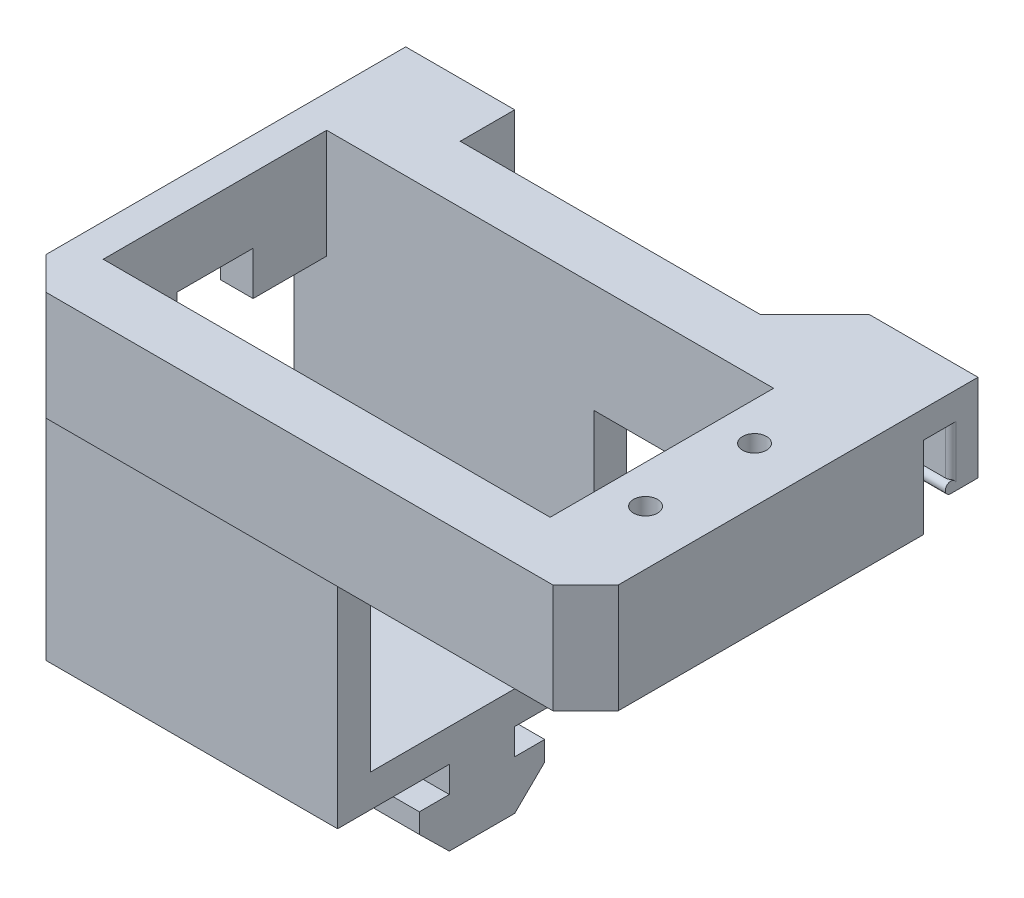
SolidWorks part; units mm, degrees
ref_plane "Alzado" through (0, 0, 0) normal (0, 0, 1) x (1, 0, 0)
ref_plane "Planta" through (0, 0, 0) normal (0, 1, 0) x (1, 0, 0)
ref_plane "Vista lateral" through (0, 0, 0) normal (1, 0, 0) x (0, 0, -1)
sketch "Croquis1" plane through (0, 0, 0) normal (0, 1, 0) x (1, 0, 0)
  line L1 (-24, 5) -> (24, 5) construction
  line L2 (-24, 5) -> (-24, -5) construction
  line L3 (-24, -5) -> (24, -5) construction
  line L4 (24, 5) -> (24, -5) construction
  line L5 (-24, 5) -> (24, -5) construction
  line L6 (-24, -5) -> (24, 5) construction
  line L7 (-20.5, 10.25) -> (20.5, 10.25)
  line L8 (-20.5, 10.25) -> (-20.5, -10.25)
  line L9 (-20.5, -10.25) -> (20.5, -10.25)
  line L10 (20.5, 10.25) -> (20.5, -10.25)
  line L11 (-20.5, 10.25) -> (20.5, -10.25) construction
  line L12 (-20.5, -10.25) -> (20.5, 10.25) construction
  line L13 (-29, 15.5) -> (29, 15.5)
  line L14 (-29, 15.5) -> (-29, -15.5)
  line L15 (-29, -15.5) -> (29, -15.5)
  line L16 (29, 15.5) -> (29, -15.5)
  line L17 (-29, 15.5) -> (29, -15.5) construction
  line L18 (-29, -15.5) -> (29, 15.5) construction
  circle A0 centre (-24, -5) radius 1.1
  circle A1 centre (24, -5) radius 1.1
  circle A2 centre (24, 5) radius 1.1
  circle A3 centre (-24, 5) radius 1.1
  point P0 (0, 0)
  point P10 (0, 0)
  point P15 (0, 0)
  dimension "D3" = 2.2
  dimension "D1" = 48
  dimension "D2" = 10
  dimension "D4" = 41
  dimension "D5" = 20.5
  dimension "D6" = 31
  dimension "D7" = 58
extrude "Saliente-Extruir1" add sketch "Croquis1" along normal blind 10
sketch "Croquis2" plane through (-29, 0, 0) normal (-1, 0, 0) x (0, 0, 1)
  line L0 (0, 0) -> (0, -9.25) construction
  line L1 (-15.5, 0) -> (15.5, 0) construction
  line L2 (-10.25, 10) -> (10.25, 10) construction
  line L3 (-10.25, -18.5) -> (10.25, -18.5)
  line L4 (-10.25, -18.5) -> (-10.25, 0)
  line L5 (-10.25, 0) -> (10.25, 0)
  line L6 (10.25, -18.5) -> (10.25, 0)
  line L7 (-10.25, -18.5) -> (10.25, 0) construction
  line L8 (-10.25, 0) -> (10.25, -18.5) construction
  line L9 (-10.25, 10) -> (10.25, 10) construction
  line L10 (-13.25, 0) -> (-13.25, -21.5)
  line L11 (-13.25, -21.5) -> (-3, -21.5)
  line L12 (13.25, -21.5) -> (13.25, 0)
  line L13 (13.25, 0) -> (10.25, 0)
  line L14 (-13.25, 0) -> (-10.25, 0)
  line L15 (-10.25, -18.5) -> (-10.25, -21.5) construction
  line L16 (0, -9.25) -> (0, -23.9) construction
  line L17 (-5.75, -23.9) -> (5.75, -23.9) construction
  line L18 (-3, -21.5) -> (-3, -23.9)
  line L19 (-3, -23.9) -> (-5.75, -23.9)
  line L20 (3, -21.5) -> (3, -23.9)
  line L21 (3, -23.9) -> (5.75, -23.9)
  line L22 (3, -21.5) -> (13.25, -21.5)
  line L23 (3, -21.5) -> (0, -21.5) construction
  line L24 (0, -21.5) -> (-3, -21.5) construction
  line L25 (-5.75, -23.9) -> (-5.75, -25.7)
  line L26 (-5.75, -25.7) -> (-3, -28.4)
  line L27 (-3, -28.4) -> (3, -28.4)
  line L28 (3, -28.4) -> (5.75, -25.7)
  line L29 (5.75, -25.7) -> (5.75, -23.9)
  point P20 (0, -23.9)
  line M21 (-15.5, 0) -> (15.5, 0)
  dimension "D1" = 18.5
  dimension "D2" = 3
  dimension "D3" = 3
  dimension "D4" = 6
  dimension "D5" = 1.8
  dimension "D6" = 4.5
  dimension "D7" = 11.5
  dimension "D8" = 2.4
  dimension "D9" = 6
extrude "Saliente-Extruir2" add sketch "Croquis2" against normal blind 33 contours L28 L29 L21 L20 L22 L12 L6 L3 L4 L10 L11 L18 L19 L25 L26 L27 M21 region at (-29, -18.8884, 0)
sketch "Croquis3" plane through (0, 0, 13.25) normal (0, 0, 1) x (1, 0, 0)
  circle A0 centre (-9.7378, -26.4) radius 2.1
  dimension "D1" = 4.2
extrude "Cortar-Extruir1" cut sketch "Croquis3" against normal through all
sketch "Croquis4" plane through (-29, 0, 0) normal (-1, 0, 0) x (0, 0, 1)
  line L0 (-10.25, -18.5) -> (10.25, -18.5) construction
  line L1 (10.25, -18.5) -> (10.25, 0) construction
  line L2 (-10.25, 0) -> (10.25, 0) construction
  line L3 (-10.25, -18.5) -> (-10.25, 0) construction
  line L4 (-10.25, -18.5) -> (10.25, -18.5)
  line L5 (10.25, -18.5) -> (10.25, 0)
  line L6 (-10.25, 0) -> (10.25, 0)
  line L7 (-10.25, -18.5) -> (-10.25, 0)
  line L18 (-15.5, 0) -> (-13.25, 0)
  line L19 (-13.25, 0) -> (-13.25, -21.5)
  line L20 (-13.25, -21.5) -> (-3, -21.5)
  line L21 (-3, -21.5) -> (-3, -23.9)
  line L22 (-3, -23.9) -> (-5.75, -23.9)
  line L23 (-5.75, -23.9) -> (-5.75, -25.7)
  line L24 (-5.75, -25.7) -> (-3, -28.4)
  line L25 (-3, -28.4) -> (3, -28.4)
  line L26 (3, -28.4) -> (5.75, -25.7)
  line L27 (5.75, -25.7) -> (5.75, -23.9)
  line L28 (5.75, -23.9) -> (3, -23.9)
  line L29 (3, -23.9) -> (3, -21.5)
  line L30 (3, -21.5) -> (13.25, -21.5)
  line L31 (13.25, -21.5) -> (13.25, 0)
  line L33 (15.5, 0) -> (15.5, 10)
  line L34 (-15.5, 0) -> (-13.25, 0)
  line L35 (-15.5, 10) -> (-15.5, 0)
  line L37 (-13.25, 0) -> (-13.25, -21.5)
  line L38 (-13.25, -21.5) -> (-3, -21.5)
  line L39 (-3, -21.5) -> (-3, -23.9)
  line L40 (-3, -23.9) -> (-5.75, -23.9)
  line L41 (-5.75, -23.9) -> (-5.75, -25.7)
  line L42 (-5.75, -25.7) -> (-3, -28.4)
  line L43 (-3, -28.4) -> (3, -28.4)
  line L44 (3, -28.4) -> (5.75, -25.7)
  line L45 (5.75, -25.7) -> (5.75, -23.9)
  line L46 (5.75, -23.9) -> (3, -23.9)
  line L47 (3, -23.9) -> (3, -21.5)
  line L48 (3, -21.5) -> (13.25, -21.5)
  line L49 (13.25, -21.5) -> (13.25, 0)
  line L51 (15.5, 0) -> (15.5, 10)
  line L53 (-15.5, 10) -> (-15.5, 0)
  line L63 (13.25, 0) -> (15.5, 0)
  line L65 (13.25, 0) -> (15.5, 0)
  line L66 (15.5, 10) -> (-15.5, 10)
  line L67 (15.5, 10) -> (-15.5, 10)
  dimension "D1" = 0
extrude "Cortar-Extruir2" cut sketch "Croquis4" against normal blind 5.5
chamfer "Chaflán1" distance 1.5 angle 45 1 edges at (-23.5, -18.5, 0)
chamfer "Chaflán2" distance 2 angle 45 2 edges at (-9.75, 0, 13.25) (-9.75, 0, -13.25)
sketch "Croquis5" plane through (0, 0, 0) normal (0, -1, 0) x (1, 0, 0)
  line L1 (-20.5, 10.25) -> (-23.5, 10.25)
  line L2 (-20.5, 10.25) -> (-20.5, -10.25)
  line L3 (-20.5, -10.25) -> (-23.5, -10.25)
  line L4 (-23.5, 10.25) -> (-23.5, -10.25)
extrude "Saliente-Extruir3" add sketch "Croquis5" against normal up to surface (10 mm away) up to face at (24, 10, -3.9)
sketch "Croquis6" plane through (-23.5, 0, 0) normal (-1, 0, 0) x (0, 0, 1)
  line L0 (0, 0) -> (0, 10) construction
  line L1 (10.25, 0) -> (-10.25, 0) construction
  line L2 (15.5, 10) -> (-15.5, 10) construction
  line L4 (3.5, 4) -> (-3.5, 4)
  line L5 (3.5, 4) -> (3.5, 0)
  line L6 (3.5, 0) -> (-3.5, 0)
  line L7 (-3.5, 4) -> (-3.5, 0)
  line L8 (3.5, 4) -> (-3.5, 0) construction
  line L9 (3.5, 0) -> (-3.5, 4) construction
  point P6 (0, 2)
  dimension "D1" = 6
  dimension "D2" = 7
extrude "Cortar-Extruir3" cut sketch "Croquis6" against normal up to next
sketch "Croquis7" plane through (0, -28.4, 0) normal (0, -1, 0) x (1, 0, 0)
  line L0 (-10.3781, 0) -> (-9.0975, 0) construction
  line L1 (-10.3781, 3) -> (-10.3781, -3) construction
  line L2 (-9.0975, -3) -> (-9.0975, 3) construction
  line L3 (-10.3781, 3) -> (-23.5, 3) construction
  line L4 (-7.7378, -3) -> (-11.7378, -3)
  line L5 (-7.7378, -3) -> (-7.7378, 3)
  line L6 (-7.7378, 3) -> (-11.7378, 3)
  line L7 (-11.7378, -3) -> (-11.7378, 3)
  line L8 (-7.7378, -3) -> (-11.7378, 3) construction
  line L9 (-7.7378, 3) -> (-11.7378, -3) construction
  point P6 (-9.7378, 0)
  dimension "D1" = 4
extrude "Saliente-Extruir4" add sketch "Croquis7" against normal blind 0.5
chamfer "Chaflán3" distance 3 angle 45 2 edges at (-23.5, 5, 15.5) (29, 5, 15.5)
ref_plane "Plano1" through (29, 0, 0) normal (1, 0, 0) x (0, 0, -1)
sketch "Croquis8" plane through (29, 0, 0) normal (1, 0, 0) x (0, 0, -1)
  line L1 (15.5, 7.5) -> (18, 7.5)
  line L2 (15.5, 7.5) -> (15.5, 3)
  line L3 (15.5, 3) -> (18, 3)
  line L4 (18, 7.5) -> (18, 3)
  line L5 (18, 2) -> (20.5, 2)
  line L6 (20.5, 2) -> (20.5, 10)
  line L7 (20.5, 10) -> (15.5, 10)
  line L8 (15.5, 10) -> (15.5, 7.5)
  arc A0 (18, 3) -> (18, 2) centre (18, 2.5) ccw
  point P4 (15.5, 10)
  point P8 (15.5, 10)
  point P12 (0, 0)
  point P14 (0, 0)
  point P15 (15.5, 7.5)
  point P16 (15.5, 7.5)
  point P17 (0, 0)
  dimension "D3" = 0.5
  dimension "D1" = 2.5
  dimension "D2" = 4.5
  dimension "D4" = 2.5
  dimension "D5" = 2.5
extrude "Saliente-Extruir5" add sketch "Croquis8" against normal blind 10 contours L4 A0 L5 L6 L7 L8 L1 region at (29, 6.5935, -18.642)
fillet "Redondeo1" radius 0.5 1 edges at (29, 5.25, -18)
sketch "Croquis9" plane through (-23.5, 0, 0) normal (-1, 0, 0) x (0, 0, 1)
  line L6 (-18, 3) -> (-18, 7.5)
  line L7 (-18, 7.5) -> (-15.5, 7.5)
  line L8 (-15.5, 7.5) -> (-15.5, 10)
  line L9 (-15.5, 10) -> (-20.5, 10)
  line L10 (-20.5, 10) -> (-20.5, 2)
  line L11 (-20.5, 2) -> (-18, 2)
  line L12 (-18, 3) -> (-18, 7.5)
  line L13 (-18, 7.5) -> (-15.5, 7.5)
  line L14 (-15.5, 7.5) -> (-15.5, 10)
  line L15 (-15.5, 10) -> (-20.5, 10)
  line L16 (-20.5, 10) -> (-20.5, 2)
  line L17 (-20.5, 2) -> (-18, 2)
  arc A1 (-18, 2) -> (-18, 3) centre (-18, 2.5) ccw
  arc A2 (-18, 2) -> (-18, 3) centre (-18, 2.5) ccw
  dimension "D1" = 0
extrude "Saliente-Extruir6" add sketch "Croquis9" against normal blind 10
chamfer "Chaflán5" distance 0.5 angle 45 2 edges at (-23.5, 3.75, -15.5) (-23.5, 5.25, -18)
chamfer "Chaflán6" distance 5 angle 45 1 edges at (19, 8.75, -15.5)
